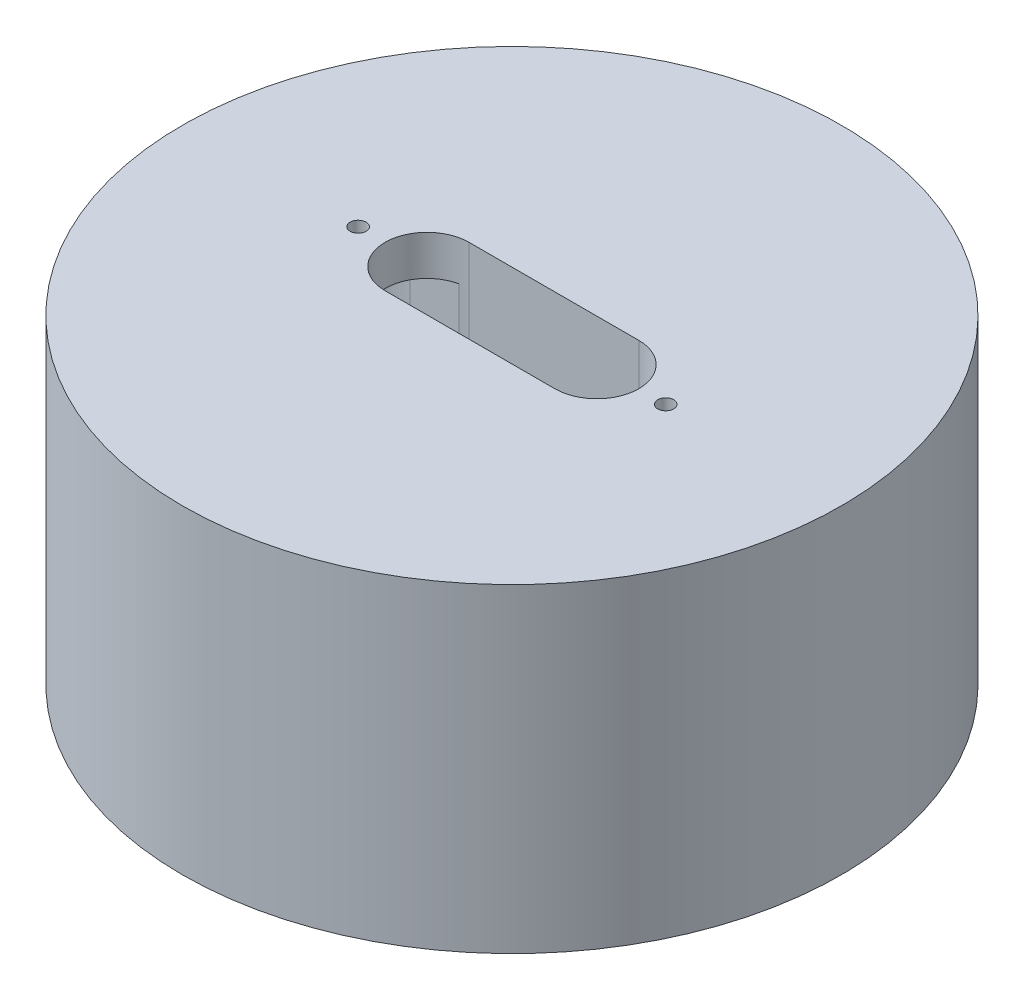
SolidWorks part; units mm, degrees
ref_plane "前视基准面" through (0, 0, 0) normal (0, 0, 1) x (1, 0, 0)
ref_plane "上视基准面" through (0, 0, 0) normal (0, 1, 0) x (1, 0, 0)
ref_plane "右视基准面" through (0, 0, 0) normal (1, 0, 0) x (0, 0, -1)
other "Configuration Table"
sketch "草图1" plane through (0, 0, 0) normal (0, 1, 0) x (1, 0, 0)
  circle A0 centre (0, 0) radius 16.5
  dimension "D1" = 33
extrude "凸台-拉伸1" add sketch "草图1" along normal blind 16
sketch "草图2" plane through (0, 0, 0) normal (0, -1, 0) x (-1, 0, 0)
  circle A0 centre (0, 0) radius 14.25
  dimension "D1" = 28.5
extrude "切除-拉伸1" cut sketch "草图2" against normal blind 5.1
sketch "草图3" plane through (0, 5.1, 0) normal (0, -1, 0) x (1, 0, 0)
  circle A0 centre (0, 0) radius 9.5
  dimension "D1" = 19
extrude "切除-拉伸2" cut sketch "草图3" against normal blind 5
sketch "草图4" plane through (0, 0, 0) normal (0, -1, 0) x (1, 0, 0)
  line L1 (4.25, 2.1) -> (-4.25, 2.1)
  line L2 (4.25, 2.1) -> (4.25, -2.1)
  line L3 (4.25, -2.1) -> (-4.25, -2.1)
  line L4 (-4.25, 2.1) -> (-4.25, -2.1)
  line L5 (4.25, 2.1) -> (-4.25, -2.1) construction
  line L6 (4.25, -2.1) -> (-4.25, 2.1) construction
  circle A0 centre (-4.25, 0) radius 2.1
  circle A1 centre (4.25, 0) radius 2.1
  dimension "D1" = 4.2
  dimension "D2" = 8.5
extrude "切除-拉伸3" cut sketch "草图4" against normal through all contours L4 A0 | A1 L1 A0 L3 | L2 A1 | L2 A1 | L4 A0 region at (0, 0, 0) region at (5.1413, 0, 0) region at (3.3587, 0, 0) region at (-3.3587, 0, 0) region at (-5.1413, 0, 0)
sketch "草图5" plane through (0, 0, 0) normal (0, -1, 0) x (1, 0, 0)
  line L1 (7.15, 2.05) -> (-7.15, 2.05)
  line L2 (7.15, 2.05) -> (7.15, -2.05)
  line L3 (7.15, -2.05) -> (-7.15, -2.05)
  line L4 (-7.15, 2.05) -> (-7.15, -2.05)
  line L5 (7.15, 2.05) -> (-7.15, -2.05) construction
  line L6 (7.15, -2.05) -> (-7.15, 2.05) construction
  circle A0 centre (-7.15, 0) radius 2.05
  circle A1 centre (7.15, 0) radius 2.05
  dimension "D1" = 4.1
  dimension "D2" = 14.3
extrude "切除-拉伸4" cut sketch "草图5" against normal offset from surface (14 mm away) 2 contours L4 A0 | L2 A1 | L1 L4 L3 L2 region at (8.02, 0, 0) region at (-8.02, 0, 0) up to face at (0, 16, 0)
sketch "草图6" plane through (0, 14, 0) normal (0, -1, 0) x (1, 0, 0)
  circle A0 centre (7.7, 0) radius 0.4
  circle A1 centre (-7.7, 0) radius 0.4
  dimension "D1" = 0.8
extrude "切除-拉伸5" cut sketch "草图6" against normal blind 2
sketch "草图7" plane through (0, 0, 0) normal (0, -1, 0) x (1, 0, 0)
  line L0 (16.5, 0) -> (15, 0) construction
  line L1 (15, 0) -> (0, 0) construction
  circle A0 centre (15, 0) radius 0.4
  circle A1 centre (0, 0) radius 16.5 construction
  dimension "D1" = 0.8
  dimension "D2" = 1.5
extrude "切除-拉伸6" cut sketch "草图7" against normal blind 3
pattern_circular "阵列(圆周)1" count 4 over 360 about axis through (0, 16, 0) along (0, -1, 0) of "切除-拉伸6" reverse direction yes
sketch "草图8" plane through (0, 0, 0) normal (0, -1, 0) x (1, 0, 0)
  line L0 (0, 0) -> (-15.0183, 2.6481)
  line L1 (0, 0) -> (-2.6481, 15.0183)
  line L2 (0, 0) -> (0, 15.25) construction
  line L3 (0, 0) -> (-15.25, 0) construction
  circle A0 centre (0, 0) radius 15.25
  circle A1 centre (0, 0) radius 14.25 construction
  circle M10 centre (0, 0) radius 14.25
  dimension "D1" = 1
  dimension "D2" = 10
  dimension "D3" = 10
extrude "切除-拉伸7" cut sketch "草图8" against normal up to surface (10.1 mm away) contours L0 L1 M10 | L1 A0 L0 M10 region at (-6.3075, 0, 6.3075) region at (-14.4951, 0, 2.736) up to face at (0, 10.1, 0)
